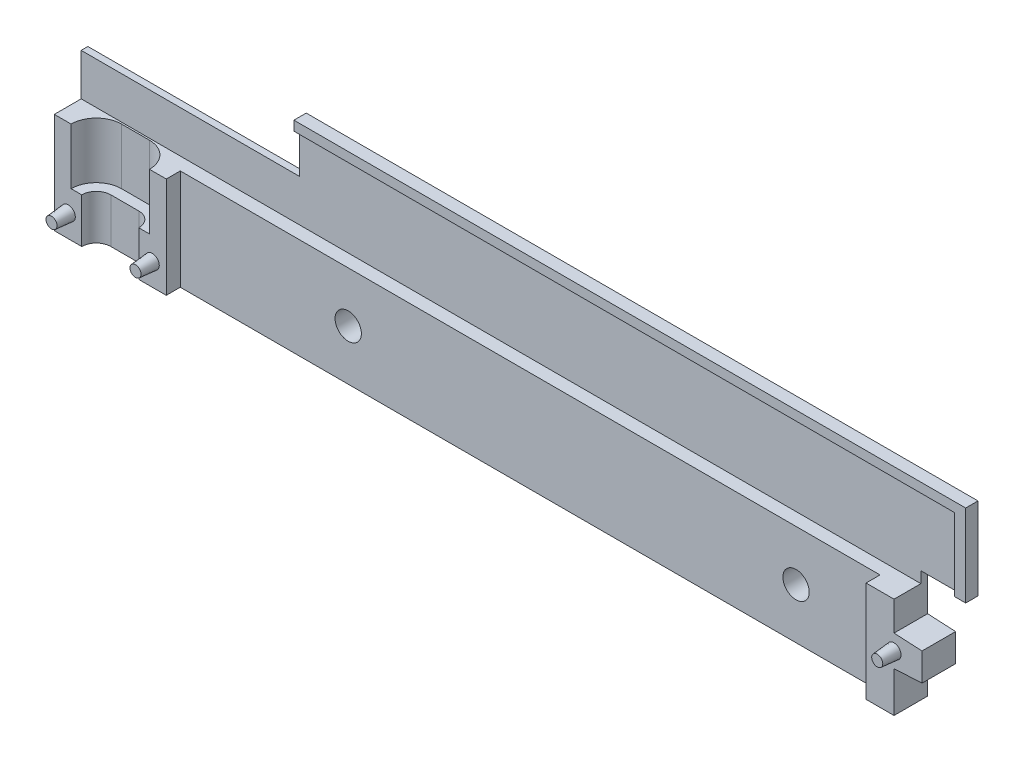
SolidWorks part; units mm, degrees
ref_plane "Front Plane" through (0, 0, 0) normal (0, 0, 1) x (1, 0, 0)
ref_plane "Top Plane" through (0, 0, 0) normal (0, 1, 0) x (1, 0, 0)
ref_plane "Right Plane" through (0, 0, 0) normal (1, 0, 0) x (0, 0, -1)
ref_axis "X-Axis" through (0, 0, 0) along (1, 0, 0)
ref_axis "Y-Axis" through (0, 42.2917, 0) along (0, -1, 0)
ref_axis "Z-Axis" through (0, 0, 55.0015) along (0, 0, -1)
sketch "Sketch1" plane through (0, 0, 0) normal (0, 0, 1) x (1, 0, 0)
  line L1 (-127.8191, -9.8629) -> (22.1809, -9.8629)
  line L2 (22.1809, -9.8629) -> (22.1809, -2.6129)
  line L3 (22.1809, -2.6129) -> (27.1809, -2.6129)
  line L4 (27.1809, -2.6129) -> (27.1809, 2.8871)
  line L5 (27.1809, 2.8871) -> (22.1809, 2.8871)
  line L6 (22.1809, 2.8871) -> (22.1809, 10.1371)
  line L7 (22.1809, 10.1371) -> (31.1809, 10.1371)
  line L8 (31.1809, 10.1371) -> (31.1809, 23.6371)
  line L10 (-127.8191, 15.6371) -> (-127.8191, -9.8629)
  line L12 (-88.8191, -25.8695) -> (-88.8191, 48.9262) construction
  line L13 (31.1809, 13.1371) -> (10.3885, 13.1371) construction
  line L14 (31.1809, 23.6371) -> (-88.8191, 23.6371) construction
  line L15 (-88.8191, 23.6371) -> (-88.8191, 15.6371)
  line L16 (-88.8191, 15.6371) -> (-127.8191, 15.6371)
  line L17 (31.1809, 23.6371) -> (31.1809, 24.8371)
  line L18 (31.1809, 24.8371) -> (-88.8191, 24.8371)
  line L19 (-88.8191, 24.8371) -> (-88.8191, 23.6371)
  point P5 (27.1809, 0.1371)
  dimension "D2" = 10
  dimension "D3" = 20
  dimension "D4" = 5.5
  dimension "D5" = 9
  dimension "D7" = 120
  dimension "D8" = 5
  dimension "D10" = 3
  dimension "D11" = 8
  dimension "D12" = 10.5
  dimension "D13" = 1.2
  dimension "D14" = 150
extrude "Boss-Extrude1" add sketch "Sketch1" along normal blind 6 and the other way blind 6
sketch "Sketch2" plane through (-127.8191, 0, 0) normal (-1, 0, 0) x (0, 0, 1)
  line L0 (-6, -9.8629) -> (6, -9.8629) construction
  line L1 (-4.8, 23.1371) -> (4.8, 23.1371) construction
  line L2 (-4.8, 23.1371) -> (-4.8, 8.1371)
  line L3 (-4.8, 8.1371) -> (4.8, 8.1371)
  line L4 (4.8, 23.1371) -> (4.8, 8.1371)
  line L5 (-6, 24.8371) -> (-6, 15.6371) construction
  line L7 (-6, 2.8871) -> (6, 2.8871) construction
  line L8 (-6, 15.6371) -> (-6, -9.8629) construction
  line L9 (6, 15.6371) -> (6, -9.8629) construction
  line L10 (0, 2.8871) -> (0, 23.1371) construction
  line L11 (-4.8, 23.1371) -> (-3.8, 23.1371)
  line L12 (-3.8, 23.1371) -> (-3.8, 24.8371)
  line L13 (-6, 24.8371) -> (6, 24.8371) construction
  line L14 (-3.8, 24.8371) -> (3.8, 24.8371)
  line L15 (3.8, 24.8371) -> (3.8, 23.1371)
  line L16 (3.8, 23.1371) -> (4.8, 23.1371)
  point P6 (0, 23.1371)
  dimension "D1" = 33
  dimension "D2" = 18
  dimension "D3" = 1
  dimension "D4" = 1
  dimension "D5" = 15
  dimension "D7" = 1.2
extrude "Cut-Extrude1" cut sketch "Sketch2" against normal offset from surface (157 mm away) 2 up to face at (31.1809, 17.4871, 0)
sketch "Sketch8" plane through (0, 0, 0) normal (0, 0, 1) x (1, 0, 0)
  line L0 (-127.8191, 15.6371) -> (-127.8191, -9.8629) construction
  line L1 (-107.8191, 24.8371) -> (17.1809, 24.8371)
  line L2 (-107.8191, 24.8371) -> (-107.8191, -9.8629)
  line L3 (-107.8191, -9.8629) -> (17.1809, -9.8629)
  line L4 (17.1809, 24.8371) -> (17.1809, -9.8629)
  line L5 (-127.8191, -9.8629) -> (22.1809, -9.8629) construction
  line L7 (22.1809, 2.8871) -> (22.1809, 10.1371) construction
  line L8 (29.1809, 24.8371) -> (-88.8191, 24.8371) construction
  point P12 (22.1809, 6.5121)
  dimension "D1" = 20
  dimension "D2" = 5
extrude "Cut-Extrude4" cut sketch "Sketch8" against normal blind 2.5 and the other way blind 2.5 contours L2 L3 L4 L1
sketch "Sketch9" plane through (0, 0, 0) normal (0, 0, 1) x (1, 0, 0)
  line L0 (-107.8191, -0.8629) -> (17.1809, -0.8629) construction
  line L1 (-107.8191, 8.1371) -> (-107.8191, -9.8629) construction
  line L2 (17.1809, 8.1371) -> (17.1809, -9.8629) construction
  circle A0 centre (-77.8191, -0.8629) radius 2.35
  circle A1 centre (2.1809, -0.8629) radius 2.35
  dimension "D1" = 4.7
  dimension "D2" = 80
  dimension "D3" = 15
extrude "Cut-Extrude5" cut sketch "Sketch9" against normal through all and the other way through all
chamfer "Chamfer2" distance 5 angle 3 2 edges at (27.1809, -2.6129, 0) (27.1809, 2.8871, 0) first distance on face at (24.6809, -2.6129, 0) first distance on face at (24.6809, 2.8871, 0)
sketch "Sketch14" plane through (0, 8.1371, 0) normal (0, 1, 0) x (1, 0, 0)
  line L0 (-120.3191, 4.5) -> (-115.3191, 4.5)
  line L1 (-115.3191, -4.5) -> (-120.3191, -4.5)
  line L2 (-107.8191, 0) -> (-127.8191, 0) construction
  line L3 (-107.8191, 2.5) -> (-107.8191, -2.5) construction
  line L5 (-127.8191, 4.8) -> (-127.8191, -4.8) construction
  arc A0 (-115.3191, 4.5) -> (-115.3191, -4.5) centre (-115.3191, 0) cw
  arc A1 (-120.3191, -4.5) -> (-120.3191, 4.5) centre (-120.3191, 0) cw
  point P16 (-117.8191, 0)
  dimension "D1" = 4.5
  dimension "D2" = 5
  dimension "D3" = 2.5
extrude "Cut-Extrude8" cut sketch "Sketch14" against normal blind 10
sketch "Sketch15" plane through (0, -1.8629, 0) normal (0, 1, 0) x (1, 0, 0)
  line L7 (-120.3191, -2.6) -> (-115.3191, -2.6)
  line L8 (-115.3191, 2.6) -> (-120.3191, 2.6)
  arc A2 (-120.3191, 4.5) -> (-120.3191, -4.5) centre (-120.3191, 0) ccw construction
  arc A3 (-115.3191, -4.5) -> (-115.3191, 4.5) centre (-115.3191, 0) ccw construction
  arc A6 (-120.3191, 2.6) -> (-120.3191, -2.6) centre (-120.3191, 0) ccw
  arc A7 (-115.3191, -2.6) -> (-115.3191, 2.6) centre (-115.3191, 0) ccw
  dimension "D2" = 2.6
extrude "Cut-Extrude9" cut sketch "Sketch15" against normal through all
sketch "Sketch16" plane through (0, 0, 0) normal (0, 0, 1) x (1, 0, 0)
  line L1 (-137.4451, 59.0989) -> (76.8996, 59.0989)
  line L2 (-137.4451, 59.0989) -> (-137.4451, -25.5467)
  line L3 (-137.4451, -25.5467) -> (76.8996, -25.5467)
  line L4 (76.8996, 59.0989) -> (76.8996, -25.5467)
extrude "Cut-Extrude10" cut sketch "Sketch16" along normal through all
sketch "Sketch17" plane through (0, 0, 0) normal (0, 0, 1) x (1, 0, 0)
  line L1 (31.1809, 24.8371) -> (29.1809, 24.8371)
  line L2 (31.1809, 24.8371) -> (31.1809, 10.1371)
  line L3 (31.1809, 10.1371) -> (29.1809, 10.1371)
  line L4 (29.1809, 24.8371) -> (29.1809, 10.1371)
extrude "Cut-Extrude11" cut sketch "Sketch17" against normal up to surface (3.8 mm away) up to face at (-29.8191, 23.9871, -3.8)
sketch "Sketch19" plane through (0, 0, 0) normal (0, 0, 1) x (1, 0, 0)
  line L0 (17.1809, 0.1371) -> (27.1809, 0.1371) construction
  line L1 (27.1809, 2.6251) -> (27.1809, -2.3509) construction
  line L3 (-125.3191, -5.8629) -> (-110.3191, -5.8629) construction
  line L5 (-117.8191, -9.8629) -> (-117.8191, -1.8629) construction
  line L8 (17.1809, 8.1371) -> (17.1809, -9.8629) construction
  line L11 (-115.3191, -9.8629) -> (-120.3191, -9.8629) construction
  line L12 (-115.3191, -1.8629) -> (-120.3191, -1.8629) construction
  circle A0 centre (-125.3191, -5.8629) radius 1.25
  circle A1 centre (-110.3191, -5.8629) radius 1.25
  circle A2 centre (22.1809, 0.1371) radius 1.25
  point P17 (-117.8191, -5.8629)
  dimension "D2" = 2.5
  dimension "D1" = 15
extrude "Boss-Extrude5" add sketch "Sketch19" along normal blind 3 separate body
chamfer "Chamfer3" distance 3 angle 5 1 edges at (23.4309, 0.1371, 3) first distance on face at (23.4309, 0.1371, 3)
chamfer "Chamfer4" distance 3 angle 5 1 edges at (-109.0691, -5.8629, 3) first distance on face at (-109.0691, -5.8629, 3)
chamfer "Chamfer5" distance 3 angle 5 1 edges at (-124.0691, -5.8629, 3) first distance on face at (-124.0691, -5.8629, 3)
equation "\"Largeur Bande\"= 8.3"
equation "\"Largeur Feeder\"= \"Largeur Rail\" + 1.2 + 1.2 + 0.3"
equation "\"Largeur Rail\"= \"Largeur Bande\" + 1"
equation "\"D1@Boss-Extrude1\"=\"Largeur Feeder\"/2"
equation "\"D2@Boss-Extrude1\"=\"Largeur Feeder\"/2"
